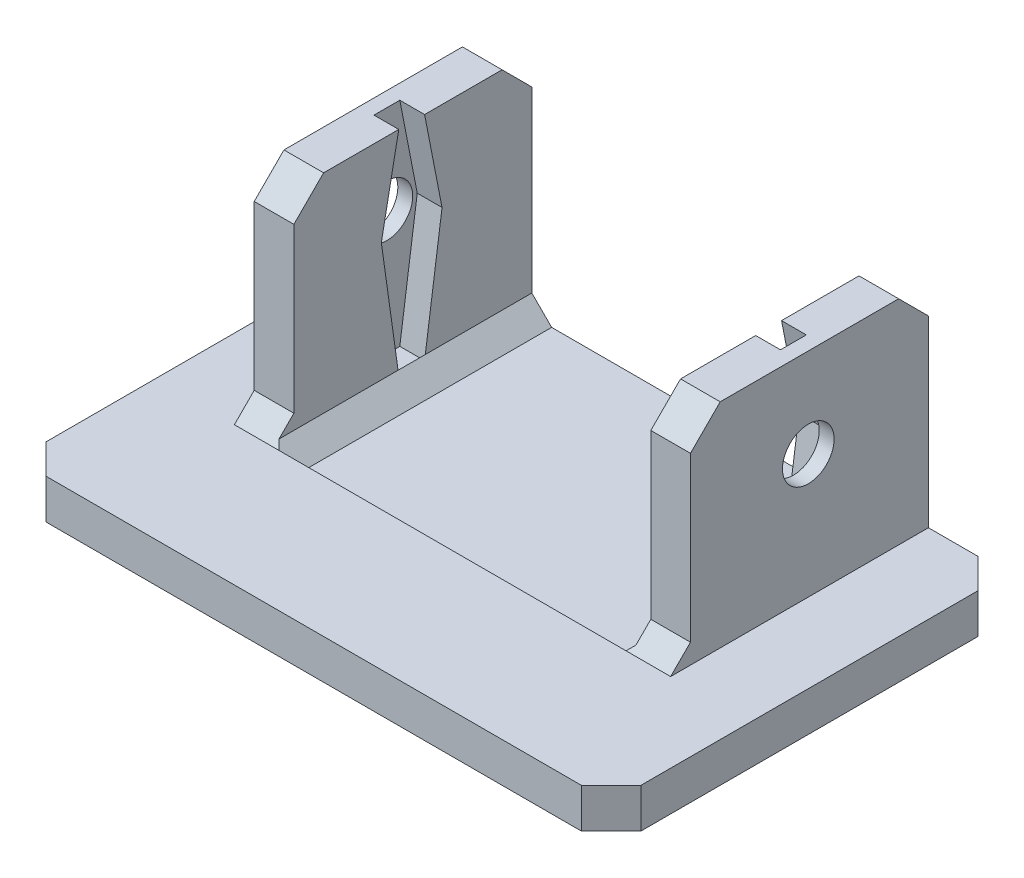
SolidWorks part; units mm, degrees
ref_plane "Front Plane" through (0, 0, 0) normal (0, 0, 1) x (1, 0, 0)
ref_plane "Top Plane" through (0, 0, 0) normal (0, 1, 0) x (1, 0, 0)
ref_plane "Right Plane" through (0, 0, 0) normal (1, 0, 0) x (0, 0, -1)
sketch "Sketch1" plane through (0, 0, 0) normal (0, 1, 0) x (1, 0, 0)
  line L1 (0, 0) -> (60, 0)
  line L2 (0, 0) -> (0, -40)
  line L3 (0, -40) -> (60, -40)
  line L4 (60, 0) -> (60, -40)
  dimension "D1" = 60
  dimension "D2" = 40
extrude "Boss-Extrude1" add sketch "Sketch1" along normal blind 4
chamfer "Chamfer1" distance 3 angle 45 4 edges at (0, 2, 40) (0, 2, 0) (60, 2, 0) (60, 2, 40)
sketch "Sketch2" plane through (0, 4, 0) normal (0, 1, 0) x (1, 0, 0)
  line L1 (12, 0) -> (48, 0)
  line L2 (12, 0) -> (12, -24)
  line L3 (12, -24) -> (48, -24)
  line L4 (48, 0) -> (48, -24)
  line L5 (60, -37) -> (60, -3) construction
  dimension "D1" = 36
  dimension "D2" = 24
  dimension "D3" = 12
extrude "Cut-Extrude1" cut sketch "Sketch2" against normal blind 1.5
sketch "Sketch3" plane through (0, 2.5, 0) normal (0, 1, 0) x (1, 0, 0)
  line L0 (30, 0) -> (30, 14.7408) construction
  line L1 (48, 0) -> (52, 0)
  line L2 (48, 0) -> (48, -24)
  line L3 (48, -24) -> (52, -24)
  line L4 (52, 0) -> (52, -24)
  line L5 (48, 0) -> (12, 0) construction
  line L6 (12, 0) -> (8, 0)
  line L7 (12, 0) -> (12, -24)
  line L8 (8, 0) -> (8, -24)
  line L9 (12, -24) -> (8, -24)
  dimension "D1" = 4
extrude "Boss-Extrude2" add sketch "Sketch3" along normal blind 23
chamfer "Chamfer2" distance 3 angle 45 4 edges at (10, 25.5, 0) (10, 25.5, 24) (50, 25.5, 0) (50, 25.5, 24)
chamfer "Chamfer3" distance 2 angle 45 2 edges at (50, 4, 24) (10, 4, 24)
chamfer "Chamfer4" distance 2 angle 45 1 edges at (30, 4, 24)
chamfer "Chamfer5" distance 2 angle 45 2 edges at (12, 2.5, 12.25) (48, 2.5, 12.25)
sketch "Sketch4" plane through (48, 0, 0) normal (-1, 0, 0) x (0, 0, 1)
  line L0 (3, 25.5) -> (21, 25.5) construction
  line L1 (9.0562, 16.5) -> (10.815, 25.5)
  line L5 (26, 4) -> (0, 4) construction
  line L7 (10.815, 4) -> (9.0562, 16.5)
  line L8 (12.1179, 16.5) -> (12.1179, -4.6484) construction
  line L9 (13.4207, 4) -> (15.1795, 16.5)
  line L10 (15.1795, 16.5) -> (13.4207, 25.5)
  line L11 (10.815, 4) -> (13.4207, 4)
  line L12 (10.815, 25.5) -> (13.4207, 25.5)
  dimension "D1" = 9
extrude "Cut-Extrude2" cut sketch "Sketch4" against normal blind 2.5
sketch "Sketch7" plane through (50.5, 0, 0) normal (-1, 0, 0) x (0, 0, 1)
  line L0 (12.1179, 25.5) -> (12.1179, 5.9876) construction
  line L1 (13.4207, 25.5) -> (10.815, 25.5) construction
  circle A0 centre (12.1179, 16.5) radius 2.604
  dimension "D1" = 9
extrude "Cut-Extrude3" cut sketch "Sketch7" against normal through all
ref_plane "Plane1" through (12, 0, 0) normal (-1, 0, 0) x (0, 0, 1)
sketch "Sketch11" plane through (12, 0, 0) normal (-1, 0, 0) x (0, 0, 1)
  line L1 (9.0562, 16.5) -> (10.815, 25.5)
  line L7 (10.815, 4) -> (9.0562, 16.5)
  line L8 (12.1179, 16.5) -> (12.1179, -4.6484) construction
  line L9 (13.4207, 4) -> (15.1795, 16.5)
  line L10 (15.1795, 16.5) -> (13.4207, 25.5)
  line L11 (10.815, 4) -> (13.4207, 4)
  line L12 (10.815, 25.5) -> (13.4207, 25.5)
extrude "Cut-Extrude4" cut sketch "Sketch11" along normal blind 2.5
sketch "Sketch12" plane through (12, 0, 0) normal (-1, 0, 0) x (0, 0, 1)
  line L0 (12.1179, 25.5) -> (12.1179, 5.9876) construction
  circle A0 centre (12.1179, 16.5) radius 2.604
  dimension "D1" = 9
extrude "Cut-Extrude6" cut sketch "Sketch12" along normal through all
